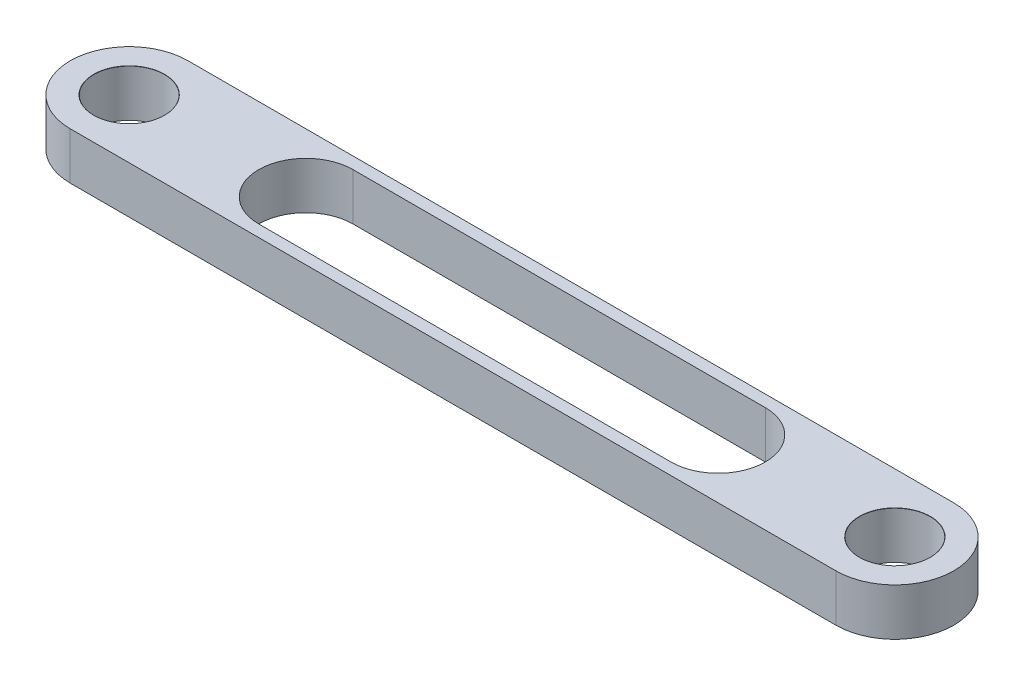
SolidWorks part; units mm, degrees
ref_plane "Plan de face" through (0, 0, 0) normal (0, 0, 1) x (1, 0, 0)
ref_plane "Plan de dessus" through (0, 0, 0) normal (0, 1, 0) x (1, 0, 0)
ref_plane "Plan de droite" through (0, 0, 0) normal (1, 0, 0) x (0, 0, -1)
sketch "Esquisse1" plane through (0, 0, 0) normal (0, 1, 0) x (1, 0, 0)
  line L0 (0, 10) -> (130, 10)
  line L1 (0, -10) -> (130, -10)
  line L2 (30, 8) -> (100, 8)
  line L3 (30, -8) -> (100, -8)
  line L4 (0, 0) -> (30, 0) construction
  arc A0 (0, 10) -> (0, -10) centre (0, 0) ccw
  arc A1 (130, -10) -> (130, 10) centre (130, 0) ccw
  arc A2 (30, 8) -> (30, -8) centre (30, 0) ccw
  arc A3 (100, -8) -> (100, 8) centre (100, 0) ccw
  dimension "D1" = 10
  dimension "D4" = 8
  dimension "D7" = 8
  dimension "D3" = 10
  dimension "D2" = 130
  dimension "D5" = 30
  dimension "D6" = 30
extrude "Boss.-Extru.1" add sketch "Esquisse1" along normal mid plane 8
sketch "Esquisse2" plane through (0, 4, 0) normal (0, 1, 0) x (1, 0, 0)
  line L0 (22, 0) -> (0, 0) construction
  line L1 (108, 0) -> (130, 0) construction
  arc A0 (30, 8) -> (30, -8) centre (30, 0) ccw construction
  arc A1 (100, -8) -> (100, 8) centre (100, 0) ccw construction
  point P1 (0, 0)
  point P7 (130, 0)
  point P15 (0, 0)
  point P18 (130, 0)
hole_wizard "Dégagement M101" positions "Esquisse2" profile "Esquisse4" hole size "M10" standard "ISO" end condition through all
sketch "Esquisse4" plane through (130, 4, 0) normal (1, 0, 0) x (0, 0, 1)
  line L0 (0, 0) -> (0, 8)
  line L1 (0, 8) -> (6, 8)
  line L2 (6, 8) -> (6, 0.025)
  line L3 (6, 0.025) -> (6.025, 0)
  line L5 (6.025, 0) -> (0, 0)
  line L6 (-6, 0.025) -> (-6.025, 0) construction
  line L11 (0, -6.35) -> (0, 107.95) construction
  dimension "Diamètre du perçage jusqu'au prochain" = 12
  dimension "Profondeur du perçage jusqu'au prochain" = 8
  dimension "Diamètre du fraisage entrant" = 12.05
  dimension "Angle du fraisage entrant" = 90
